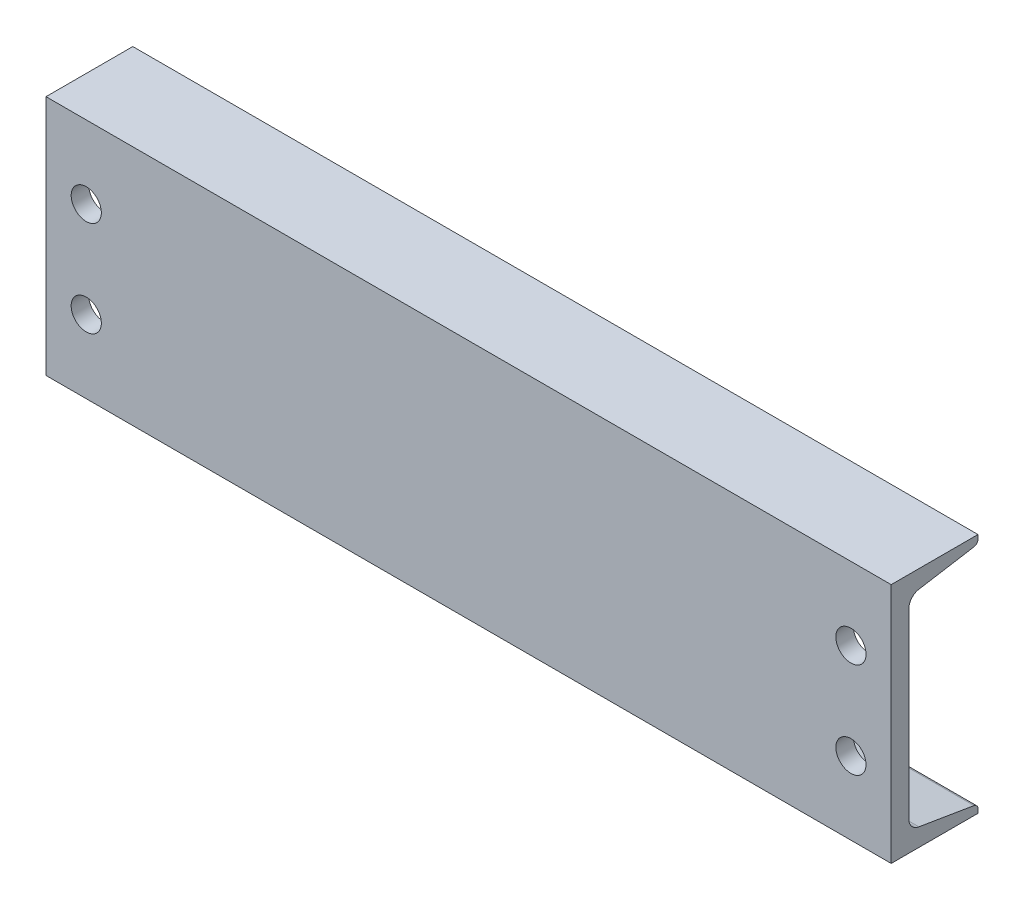
SolidWorks part; units mm, degrees
ref_plane "Front Plane" through (0, 0, 0) normal (0, 0, 1) x (1, 0, 0)
ref_plane "Top Plane" through (0, 0, 0) normal (0, 1, 0) x (1, 0, 0)
ref_plane "Right Plane" through (0, 0, 0) normal (1, 0, 0) x (0, 0, -1)
sketch "Sketch1" plane through (0, 0, 0) normal (1, 0, 0) x (0, 0, -1)
  line L0 (-27.3939, -76.2) -> (-27.3939, 76.2)
  line L1 (-27.3939, 76.2) -> (27.3939, 76.2)
  line L2 (-27.3939, -76.2) -> (27.3939, -76.2)
  line L3 (4.3561, -67.4878) -> (-21.0439, -67.4878) construction
  line L4 (-16.2941, 57.3918) -> (-16.2941, -57.3918)
  line L5 (27.3939, 76.2) -> (27.3939, 73.7107)
  line L6 (27.3939, -76.2) -> (27.3939, -73.7107)
  line L7 (-9.9269, 64.9081) -> (24.847, 70.7042)
  line L8 (-9.9269, -64.9081) -> (24.847, -70.7042)
  arc A0 (-16.2941, -57.3918) -> (-9.9269, -64.9081) centre (-8.6741, -57.3918) ccw
  arc A1 (-16.2941, 57.3918) -> (-9.9269, 64.9081) centre (-8.6741, 57.3918) cw
  arc A2 (27.3939, 73.7107) -> (24.847, 70.7042) centre (24.3459, 73.7107) cw
  arc A3 (27.3939, -73.7107) -> (24.847, -70.7042) centre (24.3459, -73.7107) ccw
extrude "Boss-Extrude1" add sketch "Sketch1" along normal mid plane 533.4
sketch "Sketch2" plane through (0, 0, 27.3939) normal (0, 0, 1) x (1, 0, 0)
  line L0 (0, 76.2) -> (0, -76.2) construction
  line L1 (266.7, 76.2) -> (-266.7, 76.2) construction
  line L2 (266.7, -76.2) -> (-266.7, -76.2) construction
  line L3 (-266.7, 0) -> (266.7, 0) construction
  line L4 (-266.7, 76.2) -> (-266.7, -76.2) construction
  line L5 (266.7, 76.2) -> (266.7, -76.2) construction
  circle A0 centre (-241.3, 30.1625) radius 9.525
  circle A1 centre (-241.3, -30.1625) radius 9.525
  circle A2 centre (241.3, -30.1625) radius 9.525
  circle A3 centre (241.3, 30.1625) radius 9.525
  dimension "D1" = 19.05
  dimension "D2" = 46.0375
  dimension "D3" = 25.4
extrude "Cut-Extrude1" cut sketch "Sketch2" against normal up to next
sketch "Sketch3" plane through (0, -76.2, 0) normal (0, -1, 0) x (1, 0, 0)
  line L0 (0, 27.3939) -> (0, -27.3939) construction
  line L1 (266.7, 27.3939) -> (-266.7, 27.3939) construction
  line L2 (266.7, -27.3939) -> (-266.7, -27.3939) construction
  line L3 (-266.7, 27.3939) -> (-266.7, -27.3939) construction
  circle A0 centre (-152.4, -10.7061) radius 9.525
  circle A1 centre (152.4, -10.7061) radius 9.525
  dimension "D3" = 19.05
  dimension "D1" = 38.1
  dimension "D2" = 114.3
extrude "Cut-Extrude2" cut sketch "Sketch3" against normal up to next
